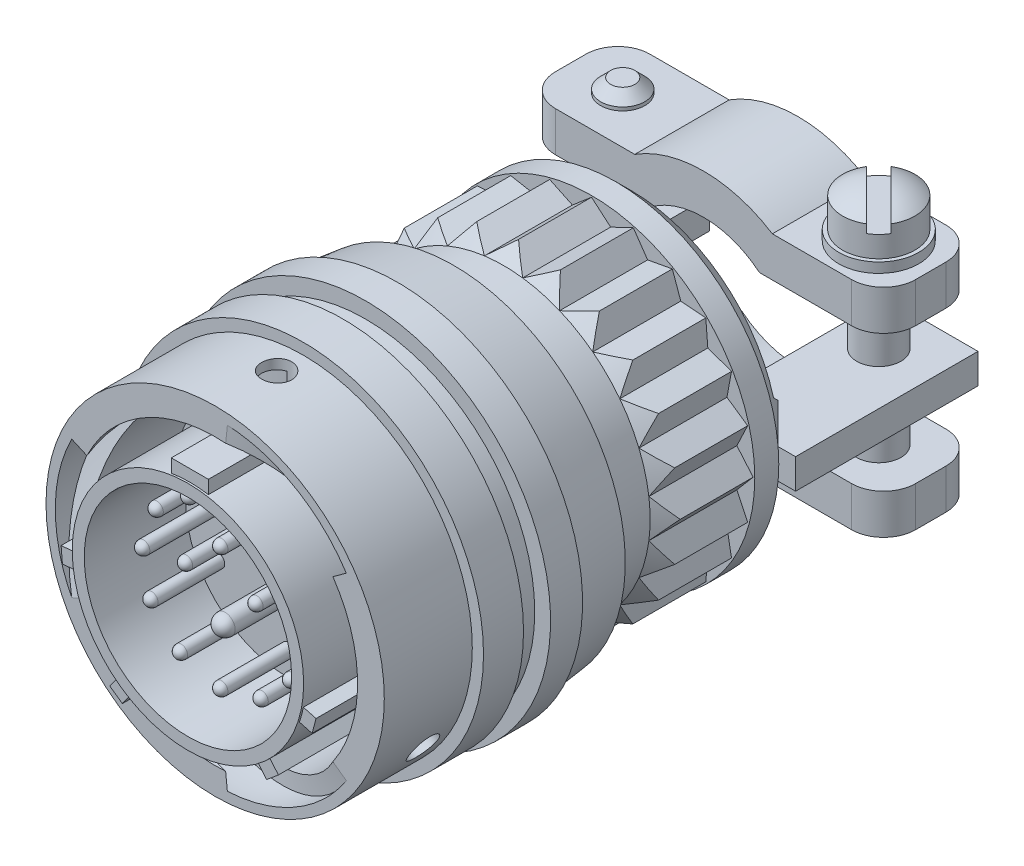
SolidWorks part; units mm, degrees
ref_plane "Front Plane" through (0, 0, 0) normal (0, 0, 1) x (1, 0, 0)
ref_plane "Top Plane" through (0, 0, 0) normal (0, 1, 0) x (1, 0, 0)
ref_plane "Right Plane" through (0, 0, 0) normal (1, 0, 0) x (0, 0, -1)
sketch "Sketch1" plane through (0, 0, 0) normal (1, 0, 0) x (0, 0, -1)
  line L0 (0, 0) -> (48.4124, 0) construction
  line L1 (0, 14.6812) -> (0, -14.6812) construction
  line L2 (48.4124, 7.0104) -> (48.4124, -7.0104) construction
  line L3 (48.4124, 4.7625) -> (48.4124, -4.7625) construction
  line L4 (0, 11.303) -> (0, -11.303) construction
  line L6 (0, 8.2296) -> (0, -8.2296) construction
  line L7 (0, 9.1821) -> (0, -9.1821) construction
  line L8 (7.9502, 8.1407) -> (7.9502, -8.1407) construction
  line L9 (21.2344, 10.3187) -> (21.2344, -10.3187) construction
  line L10 (21.2344, 10.3187) -> (19.9644, 10.3187) construction
  line L12 (23.0124, 9.525) -> (23.0124, -9.525) construction
  line L13 (0, 0) -> (7.9502, 0) construction
  line L14 (23.0124, 9.3726) -> (23.0124, -9.3726) construction
  line L15 (9.2202, 10.2235) -> (9.2202, -10.2235) construction
  line L16 (0, 12.7) -> (0, -12.7) construction
  point P12 (0.1524, 0)
  point P14 (7.9502, 0)
  point P21 (2.159, 0)
  point P22 (5.842, 0)
  point P25 (21.2344, 0)
  point P30 (13.8684, 0)
  point P34 (23.0124, 0)
  point P42 (9.2202, 0)
  dimension "D2" = 1.778
  dimension "D1" = 7.366
sketch "Sketch2" plane through (0, 0, 0) normal (0, 0, 1) x (1, 0, 0)
  line L0 (-14.2875, 0) -> (14.2875, 0) construction
  circle A0 centre (0, 0) radius 9.1821 construction
  circle A1 centre (0, 0) radius 10.2235 construction
  circle A2 centre (0, 0) radius 14.6812 construction
  circle A3 centre (0, 0) radius 12.7 construction
  dimension "H" = 28.575
sketch "Sketch3" plane through (0, 0, 0) normal (1, 0, 0) x (0, 0, -1)
  line L0 (0, 0) -> (48.4124, 0) construction
  line L1 (9.7282, 10.2235) -> (9.7282, 9.525)
  line L2 (0, 9.1821) -> (9.2202, 9.1821)
  line L3 (0, 9.1821) -> (0, 8.2296)
  line L4 (0, 8.2296) -> (21.2344, 8.2296)
  line L5 (21.2344, 9.525) -> (23.0124, 9.525)
  line L6 (9.7282, 9.525) -> (13.8684, 9.525)
  line L7 (7.9502, 8.1407) -> (21.2344, 8.1407)
  line L8 (7.9502, 8.1407) -> (7.9502, 0)
  line L9 (7.9502, 0) -> (21.2344, 0)
  line L10 (21.2344, 8.1407) -> (21.2344, 0)
  line L11 (23.0124, 9.525) -> (23.0124, -9.525) construction
  line L12 (23.0124, 9.525) -> (23.0124, 9.3726)
  line L13 (21.2344, 10.3187) -> (21.2344, -10.3187) construction
  line L25 (23.0124, 9.3726) -> (21.2344, 9.3726)
  line L26 (21.2344, 9.3726) -> (21.2344, 8.2296)
  line L28 (21.2344, 9.525) -> (20.4406, 10.3187)
  line L29 (20.4406, 10.3187) -> (14.6621, 10.3187)
  line L30 (14.6621, 10.3187) -> (13.8684, 9.525)
  line L31 (9.7282, 10.2235) -> (9.2202, 10.2235)
  line L32 (13.8684, 9.525) -> (13.8684, 10.3187) construction
  line L33 (13.8684, 10.3187) -> (14.6621, 10.3187) construction
  line L35 (9.2202, 10.2235) -> (9.2202, 9.1821)
  dimension "D2" = 0.508
  dimension "D3" = 45
revolve "Revolve1" add sketch "Sketch3" angle 360 about L0
sketch "Sketch4" plane through (0, 0, 0) normal (0, 0, 1) x (1, 0, 0)
  line L0 (-1.4732, 10.1168) -> (1.4732, 10.1168)
  line L1 (0, 10.1168) -> (0, 0) construction
  line L2 (0, 0) -> (9.8576, -2.6413) construction
  line L3 (0, 0) -> (6.5598, -7.8177) construction
  line L4 (0, 0) -> (-5.8535, -8.3597) construction
  line L5 (0, 0) -> (-10.1665, -0.8895) construction
  line L6 (10.0153, -2.0525) -> (9.6998, -3.2302)
  line L7 (7.0268, -7.4259) -> (6.0929, -8.2096)
  line L8 (-5.3542, -8.7094) -> (-6.3529, -8.01)
  line L9 (-10.1133, -1.4967) -> (-10.2196, -0.2822)
  line L10 (10.0153, -2.0525) -> (9.0074, -1.7824)
  line L11 (9.6998, -3.2302) -> (8.6919, -2.9601)
  line L12 (7.0268, -7.4259) -> (6.3561, -6.6265)
  line L13 (6.0929, -8.2096) -> (5.4221, -7.4102)
  line L14 (-5.3542, -8.7094) -> (-4.7557, -7.8546)
  line L15 (-6.3529, -8.01) -> (-5.7544, -7.1553)
  line L16 (-10.1133, -1.4967) -> (-9.0738, -1.4058)
  line L17 (-10.2196, -0.2822) -> (-9.1801, -0.1912)
  line L18 (-1.4732, 10.1168) -> (-1.4732, 9.0631)
  line L19 (1.4732, 10.1168) -> (1.4732, 9.0631)
  arc A0 (5.4221, -7.4102) -> (6.3561, -6.6265) centre (0, 0) ccw
  arc A1 (8.6919, -2.9601) -> (9.0074, -1.7824) centre (0, 0) ccw
  circle A2 centre (0, 0) radius 9.1821 construction
  circle A3 centre (0, 0) radius 10.2235 construction
  arc A4 (-5.7544, -7.1553) -> (-4.7557, -7.8546) centre (0, 0) ccw
  circle A5 centre (0, 0) radius 10.2235 construction
  arc A6 (-9.1801, -0.1912) -> (-9.0738, -1.4058) centre (0, 0) ccw
  arc A7 (1.4732, 9.0631) -> (-1.4732, 9.0631) centre (0, 0) ccw
  dimension "D1" = 2.9464
  dimension "D2" = 105
  dimension "D3" = 140
  dimension "D4" = 215
  dimension "D5" = 265
  dimension "D6" = 1.2192
extrude "Boss-Extrude1" add sketch "Sketch4" against normal up to vertex (9.2202 mm away) from vertex at -0.1524 starting at point (0, 0, -0.1524)
sketch "Sketch5" plane through (0, 0, 0) normal (1, 0, 0) x (0, 0, -1)
  line L0 (23.0124, 0) -> (0, 0) construction
  line L1 (2.159, 13.4239) -> (2.159, 11.303)
  line L3 (17.272, 11.303) -> (17.272, 13.1826)
  line L4 (17.272, 13.1826) -> (21.082, 13.1826)
  line L5 (21.082, 13.1826) -> (21.082, 13.6271)
  line L6 (2.159, 11.303) -> (17.272, 11.303)
  line L7 (2.159, 13.4239) -> (9.144, 13.4239)
  line L8 (21.082, 13.6271) -> (16.637, 14.1729)
  line L9 (16.637, 14.1729) -> (16.637, 14.6812)
  line L10 (16.637, 14.6812) -> (14.097, 14.6812)
  line L11 (14.097, 14.6812) -> (14.097, 13.4239)
  line L12 (14.097, 13.4239) -> (12.319, 13.4239)
  line L13 (12.319, 13.4239) -> (12.319, 14.3129)
  line L14 (12.319, 14.3129) -> (9.144, 14.3129)
  line L16 (9.144, 14.3129) -> (9.144, 13.4239)
  dimension "D2" = 0.889
  dimension "D5" = 6.985
  dimension "D3" = 1.2573
  dimension "D4" = 18.923
  dimension "D6" = 3.175
  dimension "D7" = 1.778
  dimension "D8" = 2.54
  dimension "D9" = 1.8796
  dimension "D10" = 7
  dimension "D11" = 3.81
  dimension "D12" = 0.4445
revolve "Revolve2" add sketch "Sketch5" angle 360 about L0
sketch "Sketch6" plane through (0, 0, 0) normal (0, 1, 0) x (1, 0, 0)
  line L0 (0, 0) -> (0, 48.4124) construction
  circle A0 centre (0, 7.0358) radius 1.1938
  dimension "D1" = 2.3876
extrude "Cut-Extrude1" cut sketch "Sketch6" along normal through all
sketch "Sketch7" plane through (0, 0, -2.159) normal (0, 0, 1) x (1, 0, 0)
  circle A0 centre (0, 0) radius 11.303 construction
  circle A1 centre (0, 0) radius 11.303
  point P3 (-11.303, 0)
curve "Helix/Spiral1" pitch 19.5072 height 4.8768 turns 0.25
ref_plane "Plane2" through (-11.303, 0, -2.159) normal (0, 0.9643, -0.2649) x (-1, 0, 0)
sketch "Sketch8" plane through (-11.303, 0, -2.159) normal (0, 0.9643, -0.2649) x (-1, 0, 0)
  line L0 (-11.303, 0) -> (0, 0) construction
  line L1 (0, 0) -> (1.3831, 0) construction
  line L2 (-0.0805, 1.3462) -> (1.3115, 1.3462)
  line L3 (1.3831, 0) -> (1.3831, 2.239) construction
  line L4 (-0.0805, -1.3462) -> (1.3115, -1.3462)
  arc A0 (1.3115, -1.3462) -> (1.3115, 1.3462) centre (-11.303, 0) ccw
  arc A1 (-0.0805, -1.3462) -> (-0.0805, 1.3462) centre (-11.303, 0) ccw
  dimension "GG" = 2.6924
sweep "Cut-Sweep1" cut profiles "Sketch8" path "Helix/Spiral1"
pattern_circular "CirPattern1" count 3 over 360 about axis through (0, 0, -23.0124) along (0, 0, -1) of "Cut-Extrude1", "Cut-Sweep1"
sketch "Sketch9" plane through (0, 0, 0) normal (1, 0, 0) x (0, 0, -1)
  line L0 (18.3134, 11.6332) -> (18.3134, 10.3187)
  line L1 (18.3134, 10.3187) -> (32.0294, 10.3187)
  line L2 (32.0294, 10.3187) -> (32.0294, 7.0104)
  line L3 (32.0294, 7.0104) -> (35.2044, 7.0104)
  line L4 (0, 0) -> (48.4124, 0) construction
  line L5 (18.3134, 11.6332) -> (32.0294, 11.6332)
  line L6 (33.9344, 12.954) -> (35.2044, 11.684)
  line L7 (32.0294, 12.954) -> (33.9344, 12.954)
  line L8 (35.2044, 11.684) -> (35.2044, 7.0104)
  line L9 (32.0294, 12.954) -> (32.0294, 11.6332)
  dimension "D1" = 16.891
  dimension "D2" = 13.716
  dimension "D3" = 1.3145
  dimension "D4" = 5.9436
  dimension "D5" = 1.27
  dimension "D6" = 45
  dimension "D7" = 13.716
  dimension "D11" = 13.208
revolve "Revolve3" add sketch "Sketch9" angle 360 about L4
sketch "Sketch10" plane through (0, 0, -32.0294) normal (0, 0, 1) x (1, 0, 0)
  line L0 (0, 11.6332) -> (0, 0) construction
  line L1 (0, 0) -> (-1.5184, 11.5337) construction
  line L2 (0, 0) -> (1.5184, 11.5337) construction
  line L3 (-1.5184, 11.5337) -> (0, 12.827)
  line L4 (0, 12.827) -> (1.5184, 11.5337)
  line L5 (0, 11.6332) -> (0, 12.827) construction
  circle A0 centre (0, 0) radius 11.6332 construction
  arc A1 (1.5184, 11.5337) -> (-1.5184, 11.5337) centre (0, 0) ccw
  circle A3 centre (0, 0) radius 12.954 construction
  dimension "D1" = 15
extrude "Boss-Extrude2" add sketch "Sketch10" along normal blind 6.985
pattern_circular "CirPattern2" count 24 over 360 about axis through (0, 0, 0) along (0, 0, 1) of "Boss-Extrude2"
sketch "Sketch11" plane through (0, 0, 0) normal (1, 0, 0) x (0, 0, -1)
  line L0 (32.0294, 0) -> (0, 0) construction
  line L1 (25.0444, 12.827) -> (25.0444, 11.6332)
  line L2 (25.0444, 11.6332) -> (26.2382, 12.827)
  line L3 (25.0444, 12.827) -> (32.0294, 12.827) construction
  line L4 (26.2382, 12.827) -> (25.0444, 12.827)
  dimension "D1" = 45
revolve "Cut-Revolve1" cut sketch "Sketch11" angle 360 about L0
sketch "Sketch12" plane through (0, 0, -35.2044) normal (0, 0, -1) x (-1, 0, 0)
  line L0 (0, 7.0104) -> (0, -7.0104) construction
  line L1 (-14.2875, 1.1875) -> (-7.0104, 1.1875)
  line L2 (-14.2875, 1.1875) -> (-14.2875, -1.1875)
  line L3 (-14.2875, -1.1875) -> (-7.0104, -1.1875)
  line L4 (-7.0104, 1.1875) -> (-7.0104, -1.1875)
  line L5 (7.0104, 1.1874) -> (7.0104, -1.1874)
  line L6 (14.2875, -1.1875) -> (7.0104, -1.1874)
  line L7 (14.2875, 1.1875) -> (14.2875, -1.1875)
  line L8 (14.2875, 1.1875) -> (7.0104, 1.1874)
  line L9 (-14.2875, 0) -> (14.2875, 0) construction
  circle A0 centre (0, 0) radius 7.0104 construction
  dimension "D1" = 2.3749
extrude "Boss-Extrude3" add sketch "Sketch12" along normal up to vertex (13.208 mm away) and the other way up to vertex (1.27 mm away) up to point (0, 0, -48.4124) other way up to point (0, 12.954, -33.9344)
chamfer "Chamfer1" distance 1.905 angle 45 4 edges at (-9.317, 1.1874, -35.2044) (-9.317, -1.1874, -35.2044) (9.317, -1.1875, -35.2044) (9.317, 1.1874, -35.2044)
sketch "Sketch13" plane through (0, 0, 0) normal (0, 1, 0) x (1, 0, 0)
  line L0 (-10.16, 44.6659) -> (10.16, 44.6659) construction
  line L1 (0, 44.6659) -> (0, 48.4124) construction
  circle A0 centre (10.16, 44.6659) radius 1.7526
  circle A1 centre (-10.16, 44.6659) radius 1.7526
  dimension "D3" = 3.5052
  dimension "D1" = 20.32
  dimension "D2" = 3.7465
extrude "Cut-Extrude2" cut sketch "Sketch13" against normal up to next (1.1874 mm away) and the other way up to next (1.1874 mm away)
sketch "Sketch14" plane through (0, 0, -48.4124) normal (0, 0, -1) x (-1, 0, 0)
  line L0 (-14.2875, 5.4229) -> (-14.2875, 8.5979)
  line L1 (-14.2875, 1.1875) -> (-14.2875, -1.1875) construction
  line L2 (-14.2875, 5.4229) -> (-4.4427, 5.4229)
  line L3 (-14.2875, 8.5979) -> (-5.4606, 8.5979)
  line L4 (0, 0) -> (0, 7.0104) construction
  line L5 (14.2875, 8.5979) -> (5.4606, 8.5979)
  line L6 (14.2875, 5.4229) -> (4.4427, 5.4229)
  line L7 (14.2875, 5.4229) -> (14.2875, 8.5979)
  line L8 (0, 7.0104) -> (0, 10.1854) construction
  circle A0 centre (0, 0) radius 7.0104 construction
  arc A1 (4.4427, 5.4229) -> (-4.4427, 5.4229) centre (0, 0) ccw
  arc A3 (5.4606, 8.5979) -> (-5.4606, 8.5979) centre (0, 0) ccw
  dimension "D1" = 3.175
  dimension "D2" = 4.7625
extrude "Boss-Extrude4" add sketch "Sketch14" against normal blind 7.493 separate body
sketch "Sketch15" plane through (0, 0, 0) normal (0, 1, 0) x (1, 0, 0)
  line L0 (4.4427, 48.4124) -> (14.2875, 48.4124) construction
  line L1 (14.2875, 48.4124) -> (14.2875, 40.9194) construction
  line L2 (14.2875, 40.9194) -> (4.4427, 40.9194) construction
  line L4 (-14.2875, 48.4124) -> (-4.4427, 48.4124) construction
  line L6 (-4.4427, 40.9194) -> (-14.2875, 40.9194) construction
  line L7 (-14.2875, 40.9194) -> (-14.2875, 48.4124) construction
  line L8 (11.7475, 48.4124) -> (14.2875, 48.4124)
  line L9 (14.2875, 48.4124) -> (14.2875, 45.8724)
  line L10 (14.2875, 40.9194) -> (11.7475, 40.9194)
  line L11 (14.2875, 43.4594) -> (14.2875, 40.9194)
  line L12 (-14.2875, 48.4124) -> (-11.7475, 48.4124)
  line L13 (-14.2875, 45.8724) -> (-14.2875, 48.4124)
  line L14 (-11.7475, 40.9194) -> (-14.2875, 40.9194)
  line L15 (-14.2875, 40.9194) -> (-14.2875, 43.4594)
  arc A0 (14.2875, 45.8724) -> (11.7475, 48.4124) centre (11.7475, 45.8724) ccw
  circle A1 centre (-10.16, 44.6659) radius 1.7526
  circle A2 centre (-10.16, 44.6659) radius 1.7526
  circle A3 centre (10.16, 44.6659) radius 1.7526
  circle A4 centre (10.16, 44.6659) radius 1.7526
  arc A5 (11.7475, 40.9194) -> (14.2875, 43.4594) centre (11.7475, 43.4594) ccw
  arc A6 (-11.7475, 48.4124) -> (-14.2875, 45.8724) centre (-11.7475, 45.8724) ccw
  arc A7 (-14.2875, 43.4594) -> (-11.7475, 40.9194) centre (-11.7475, 43.4594) ccw
  dimension "D3" = 2.54
  dimension "D1" = 0
  dimension "D2" = 0
extrude "Cut-Extrude3" cut sketch "Sketch15" along normal through all
ref_plane "Plane1" through (0, 0, -44.6659) normal (0, 0, 1) x (1, 0, 0)
sketch "Sketch16" plane through (0, 0, -44.6659) normal (0, 0, 1) x (1, 0, 0)
  line L0 (10.16, 0) -> (10.16, 9.3853) construction
  line L1 (11.9126, 8.5979) -> (8.4074, 8.5979) construction
  line L2 (8.2804, 9.3853) -> (6.985, 9.3853)
  line L3 (8.2804, 9.3853) -> (8.2804, 8.5979)
  line L4 (8.2804, 8.5979) -> (6.985, 8.5979)
  line L5 (6.985, 9.3853) -> (6.985, 8.5979)
  dimension "D1" = 3.7592
  dimension "D2" = 6.35
  dimension "D3" = 0.7874
revolve "Revolve4" add sketch "Sketch16" angle 360 about L0
sketch "Sketch17" plane through (0, 0, -44.6659) normal (0, 0, 1) x (1, 0, 0)
  line L0 (10.16, 9.3853) -> (10.16, 0) construction
  line L1 (10.16, 12.7381) -> (10.16, -9.6647)
  line L2 (10.16, -9.6647) -> (9.2011, -9.6647)
  line L3 (9.2011, -9.6647) -> (8.4074, -8.871)
  line L4 (8.4074, -8.871) -> (8.4074, 9.3853)
  line L5 (8.4074, 9.3853) -> (7.2898, 9.3853)
  line L6 (7.2898, 9.3853) -> (7.2898, 11.7323)
  arc A0 (10.16, 12.7381) -> (7.2898, 11.7323) centre (10.16, 8.1401) ccw
  point P10 (8.4074, 1.1874)
  dimension "D1" = 5.7404
  dimension "D2" = 3.3528
  dimension "D3" = 0.7937
  dimension "D4" = 45
  dimension "D5" = 19.05
  dimension "D6" = 1.0058
revolve "Revolve5" add sketch "Sketch17" angle 360 about L0
sketch "Sketch18" plane through (0, 9.3853, 0) normal (0, -1, 0) x (1, 0, 0)
  line L0 (10.6511, -45.157) -> (9.6689, -44.1748) construction
  line L1 (7.6394, -46.2043) -> (8.6216, -47.1865)
  line L2 (7.6394, -46.2043) -> (11.6984, -42.1453)
  line L3 (11.6984, -42.1453) -> (12.6806, -43.1275)
  line L4 (8.6216, -47.1865) -> (12.6806, -43.1275)
  line L5 (8.4074, -44.6659) -> (7.2898, -44.6659) construction
  circle A0 centre (10.16, -44.6659) radius 2.8702 construction
  dimension "D1" = 1.3891
  dimension "D2" = 45
extrude "Cut-Extrude4" cut sketch "Sketch18" against normal through all from offset 1.6764 offset against normal yes
pattern_circular "CirPattern3" count 2 over 360 about axis through (0, 0, 0) along (0, 0, 1) of bodies 184 180 179 164 181
sketch "Sketch14-15P" plane through (0, 0, -7.9502) normal (0, 0, 1) x (1, 0, 0)
  line L0 (0, 0) -> (0, 5.715) construction
  line L1 (2.54, 5.715) -> (-2.54, 5.715) construction
  line L2 (5.1308, 3.556) -> (-5.1308, 3.556) construction
  line L3 (0, 3.556) -> (0, 0) construction
  line L4 (6.1976, 0.3556) -> (-6.1976, 0.3556) construction
  line L5 (0, 0.3556) -> (0, 0) construction
  line L6 (5.5372, -2.8702) -> (-5.5372, -2.8702) construction
  line L7 (0, -2.8702) -> (0, 0.3556) construction
  line L8 (3.2004, -5.3086) -> (-3.2004, -5.3086) construction
  line L9 (0, -5.3086) -> (0, 0) construction
  line L10 (0, -6.223) -> (0, 0) construction
  line L11 (0, 3.556) -> (0, 0) construction
  line L12 (2.794, 1.016) -> (-2.794, 1.016) construction
  line L13 (0, 1.016) -> (0, 0) construction
  line L14 (0, -1.9558) -> (0, 0) construction
  circle A0 centre (2.54, 5.715) radius 0.508
  circle A1 centre (5.1308, 3.556) radius 0.508
  circle A2 centre (6.1976, 0.3556) radius 0.508
  circle A3 centre (5.5372, -2.8702) radius 0.508
  circle A4 centre (3.2004, -5.3086) radius 0.508
  circle A5 centre (0, -6.223) radius 0.508
  circle A6 centre (-3.2004, -5.3086) radius 0.508
  circle A7 centre (-5.5372, -2.8702) radius 0.508
  circle A8 centre (-6.1976, 0.3556) radius 0.508
  circle A9 centre (-5.1308, 3.556) radius 0.508
  circle A10 centre (-2.54, 5.715) radius 0.508
  circle A11 centre (0, 3.556) radius 0.508
  circle A12 centre (2.794, 1.016) radius 0.508
  circle A13 centre (0, -1.9558) radius 0.7938
  circle A14 centre (-2.794, 1.016) radius 0.508
  dimension "D1" = 1.016
  dimension "D2" = 1.5875
  dimension "D3" = 2.54
  dimension "D4" = 5.715
  dimension "D5" = 5.1308
  dimension "D6" = 3.556
  dimension "D7" = 6.1976
  dimension "D8" = 0.3556
  dimension "D9" = 5.5372
  dimension "D10" = 2.8702
  dimension "D11" = 3.2004
  dimension "D12" = 5.3086
  dimension "D13" = 6.223
  dimension "D14" = 3.556
  dimension "D15" = 2.794
  dimension "D16" = 1.016
  dimension "D17" = 1.9558
extrude "Boss-Extrude14-15P" add sketch "Sketch14-15P" along normal up to vertex (5.7912 mm away) up to point (0, 0, -2.159)
fillet "Fillet14-15P-20" radius 0.508 14 edges at (3.048, 5.715, -2.159) (6.7056, 0.3556, -2.159) (6.0452, -2.8702, -2.159) (3.7084, -5.3086, -2.159) (0.508, -6.223, -2.159) (-2.6924, -5.3086, -2.159) (-5.0292, -2.8702, -2.159) (-5.6896, 0.3556, -2.159) (-2.286, 1.016, -2.159) (-4.6228, 3.556, -2.159) (-2.032, 5.715, -2.159) (0.508, 3.556, -2.159) (3.302, 1.016, -2.159) (5.6388, 3.556, -2.159)
fillet "Fillet14-15P-16" radius 0.7937 1 edges at (0.7937, -1.9558, -2.159)
sketch "Sketch14-19P" [suppressed] plane through (0, 0, -7.9502) normal (0, 0, 1) x (1, 0, 0)
  line L0 (0, 5.715) -> (0, -5.715) construction
  line L1 (3.302, 5.715) -> (-3.302, 5.715) construction
  line L2 (3.302, 5.715) -> (3.302, -5.715) construction
  line L3 (3.302, -5.715) -> (-3.302, -5.715) construction
  line L4 (-3.302, -5.715) -> (-3.302, 5.715) construction
  line L5 (4.953, 2.8702) -> (-4.953, 2.8702) construction
  line L6 (4.953, 2.8702) -> (4.953, -2.8702) construction
  line L7 (4.953, -2.8702) -> (-4.953, -2.8702) construction
  line L8 (-4.953, -2.8702) -> (-4.953, 2.8702) construction
  line L9 (6.604, 0) -> (-6.604, 0) construction
  line L10 (0, -2.8702) -> (0, 2.8702) construction
  line L11 (-1.651, 2.8702) -> (1.651, 2.8702) construction
  line L12 (-1.651, 2.8702) -> (-1.651, -2.8702) construction
  line L13 (-1.651, -2.8702) -> (1.651, -2.8702) construction
  line L14 (1.651, -2.8702) -> (1.651, 2.8702) construction
  circle A0 centre (0, 5.715) radius 0.508
  circle A1 centre (3.302, 5.715) radius 0.508
  circle A2 centre (4.953, 2.8702) radius 0.508
  circle A3 centre (6.604, 0) radius 0.508
  circle A4 centre (4.953, -2.8702) radius 0.508
  circle A5 centre (3.302, -5.715) radius 0.508
  circle A6 centre (0, -5.715) radius 0.508
  circle A7 centre (-3.302, -5.715) radius 0.508
  circle A8 centre (-4.953, -2.8702) radius 0.508
  circle A9 centre (-6.604, 0) radius 0.508
  circle A10 centre (-4.953, 2.8702) radius 0.508
  circle A11 centre (-3.302, 5.715) radius 0.508
  circle A12 centre (-1.651, 2.8702) radius 0.508
  circle A13 centre (1.651, 2.8702) radius 0.508
  circle A14 centre (3.302, 0) radius 0.508
  circle A15 centre (1.651, -2.8702) radius 0.508
  circle A16 centre (-1.651, -2.8702) radius 0.508
  circle A17 centre (-3.302, 0) radius 0.508
  circle A18 centre (0, 0) radius 0.508
  dimension "D1" = 1.016
  dimension "D2" = 5.715
  dimension "D3" = 3.302
  dimension "D4" = 4.953
  dimension "D5" = 2.8702
  dimension "D6" = 6.604
  dimension "D7" = 1.651
extrude "Boss-Extrude14-19P" [suppressed] add sketch "Sketch14-19P" along normal up to vertex
fillet "Fillet14-19P" [suppressed] radius 0.508
equation "\"D3@Helix/Spiral1\" = \"N@Sketch1\" - \"D@Sketch1\" - \"E@Sketch1\" + ( \"D1@Sketch6\" / 2 ) "
equation "\"D1@CirPattern2\" = 360 / \"D1@Sketch10\""
equation "\"D1@Fillet14-15P-20\" = \"D1@Sketch14-15P\" / 2"
equation "\"D1@Fillet14-15P-16\" = \"D2@Sketch14-15P\" / 2"
equation "\"D1@Fillet14-19P\" = \"D1@Sketch14-19P\" / 2"
